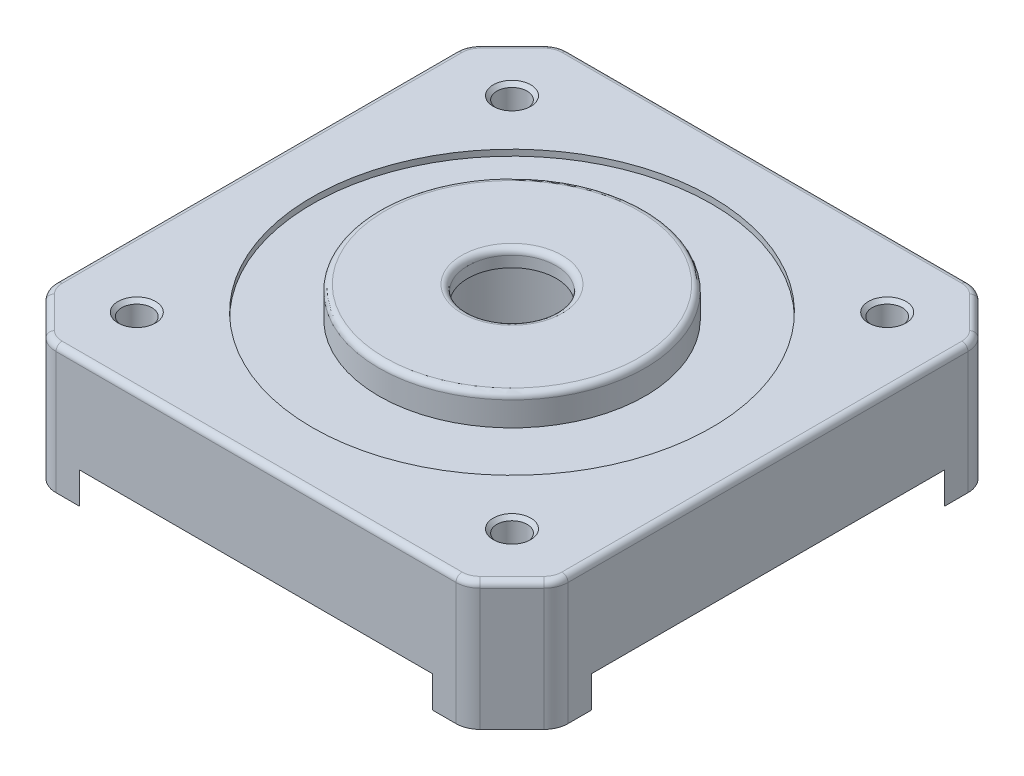
SolidWorks part; units mm, degrees
ref_plane "Спереди" through (0, 0, 0) normal (0, 0, 1) x (1, 0, 0)
ref_plane "Сверху" through (0, 0, 0) normal (0, 1, 0) x (1, 0, 0)
ref_plane "Справа" through (0, 0, 0) normal (1, 0, 0) x (0, 0, -1)
sketch "Эскиз1" plane through (0, 0, 0) normal (0, 1, 0) x (1, 0, 0)
  line L0 (-21.15, 17.35) -> (-17.35, 21.15)
  line L1 (-17.35, -21.15) -> (17.35, -21.15)
  line L2 (-21.15, -17.35) -> (-21.15, 17.35)
  line L3 (-17.35, 21.15) -> (17.35, 21.15)
  line L4 (21.15, -17.35) -> (21.15, 17.35)
  line L5 (-21.15, -21.15) -> (21.15, 21.15) construction
  line L6 (-21.15, 21.15) -> (21.15, -21.15) construction
  line L7 (17.35, 21.15) -> (21.15, 17.35)
  line L8 (17.35, -21.15) -> (21.15, -17.35)
  line L9 (-21.15, -17.35) -> (-17.35, -21.15)
  line L10 (-15.5, -15.5) -> (15.5, -15.5) construction
  line L11 (-15.5, -15.5) -> (-15.5, 15.5) construction
  line L12 (-15.5, 15.5) -> (15.5, 15.5) construction
  line L13 (15.5, -15.5) -> (15.5, 15.5) construction
  line L14 (-15.5, -15.5) -> (15.5, 15.5) construction
  line L15 (-15.5, 15.5) -> (15.5, -15.5) construction
  circle A0 centre (-15.5, 15.5) radius 1.25
  circle A1 centre (15.5, 15.5) radius 1.25
  circle A2 centre (15.5, -15.5) radius 1.25
  circle A3 centre (-15.5, -15.5) radius 1.25
  circle A4 centre (0, 0) radius 3.65
  circle A5 centre (0, 0) radius 16.5
  circle A6 centre (0, 0) radius 11
  arc A7 (-21.15, -14.6003) -> (-14.6003, -21.15) centre (0, 0) ccw
  arc A8 (-14.6003, 21.15) -> (-21.15, 14.6003) centre (0, 0) ccw
  arc A9 (21.15, 14.6003) -> (14.6003, 21.15) centre (0, 0) ccw
  arc A10 (14.6003, -21.15) -> (21.15, -14.6003) centre (0, 0) ccw
  circle A11 centre (-15.5, 15.5) radius 2.65
  circle A12 centre (15.5, 15.5) radius 2.65
  circle A13 centre (15.5, -15.5) radius 2.65
  circle A14 centre (-15.5, -15.5) radius 2.65
  point P0 (0, 0)
  point P13 (0, 0)
  dimension "D9" = 2.5
  dimension "D10" = 5.3
  dimension "D11" = 7.3
  dimension "D12" = 22
  dimension "D13" = 33
  dimension "D14" = 25.7
  dimension "D1" = 3.8
  dimension "D2" = 3.8
  dimension "D3" = 3.8
  dimension "D4" = 3.8
  dimension "D5" = 3.8
  dimension "D6" = 3.8
  dimension "D7" = 3.8
  dimension "D8" = 3.8
  dimension "D15" = 31
  dimension "D16" = 42.3
extrude "Бобышка-Вытянуть1" add sketch "Эскиз1" along normal blind 8 contours L1 A10 L4 A9 L3 A8 L2 A7 A14 A13 A12 A11 A5 | A13 A2 | A14 A3 | A11 A0 | A12 A1 | A7 L2 L9 L1 | A8 L3 L0 L2 | A9 L4 L7 L3 | A10 L1 L8 L4 region at (-18.6153, 0, -18.6153) region at (-17.7496, 0, -17.7496) region at (-18.6153, 0, 18.6153) region at (18.6153, 0, -18.6153) region at (18.6153, 0, 18.6153) region at (-18.075, 0, -15.5) region at (12.925, 0, -15.5) region at (12.925, 0, 15.5) region at (-18.075, 0, 15.5)
extrude "Бобышка-Вытянуть2" add sketch "Эскиз1<3>" along normal blind 7.5 contours A5 A6 region at (-16.0333, 0, 0)
sketch "Эскиз1<3>" plane through (0, 0, 0) normal (0, 1, 0) x (1, 0, 0) same geometry as "Эскиз1"
extrude "Бобышка-Вытянуть3" add sketch "Эскиз1<4>" along normal blind 10 contours A6 A4 region at (-10.6889, 0, 0)
sketch "Эскиз1<4>" plane through (0, 0, 0) normal (0, 1, 0) x (1, 0, 0) same geometry as "Эскиз1"
extrude "Бобышка-Вытянуть4" add sketch "Эскиз1<5>" against normal blind 2.6 contours A7 L2 L9 L1 | A10 L1 L8 L4 | A8 L3 L0 L2 | A9 L4 L7 L3 region at (-18.6153, 0, -18.6153) region at (-18.6153, 0, 18.6153) region at (18.6153, 0, -18.6153) region at (18.6153, 0, 18.6153)
sketch "Эскиз1<5>" plane through (0, 0, 0) normal (0, 1, 0) x (1, 0, 0) same geometry as "Эскиз1"
sketch "Эскиз2" plane through (0, 0, 0) normal (0, -1, 0) x (1, 0, 0)
  circle A0 centre (0, 0) radius 8
extrude "Вырез-Вытянуть1" cut sketch "Эскиз2" against normal blind 8.6
fillet "Скругление1" radius 2 8 edges at (21.15, 2.7, 17.35) (17.35, 2.7, 21.15) (-17.35, 2.7, 21.15) (-21.15, 2.7, 17.35) (-21.15, 2.7, -17.35) (-17.35, 2.7, -21.15) (17.35, 2.7, -21.15) (21.15, 2.7, -17.35)
fillet "Скругление2" radius 0.5 18 edges at (-17.2869, 8, 20.9978) (-19.25, 8, 19.25) (-20.9978, 8, 17.2869) (-21.15, 8, 0) (-20.9978, 8, -17.2869) (-19.25, 8, -19.25) (-17.2869, 8, -20.9978) (0, 8, -21.15) (17.2869, 8, -20.9978) (19.25, 8, -19.25) (20.9978, 8, -17.2869) (21.15, 8, 0) (20.9978, 8, 17.2869) (19.25, 8, 19.25) (17.2869, 8, 20.9978) (0, 8, 21.15) (0, 10, 3.65) (0, 10, 11)
chamfer "Фаска1" distance 0.3 angle 45 4 edges at (-15.5, 8, 16.75) (-15.5, 8, -14.25) (15.5, 8, -14.25) (15.5, 8, 16.75)
